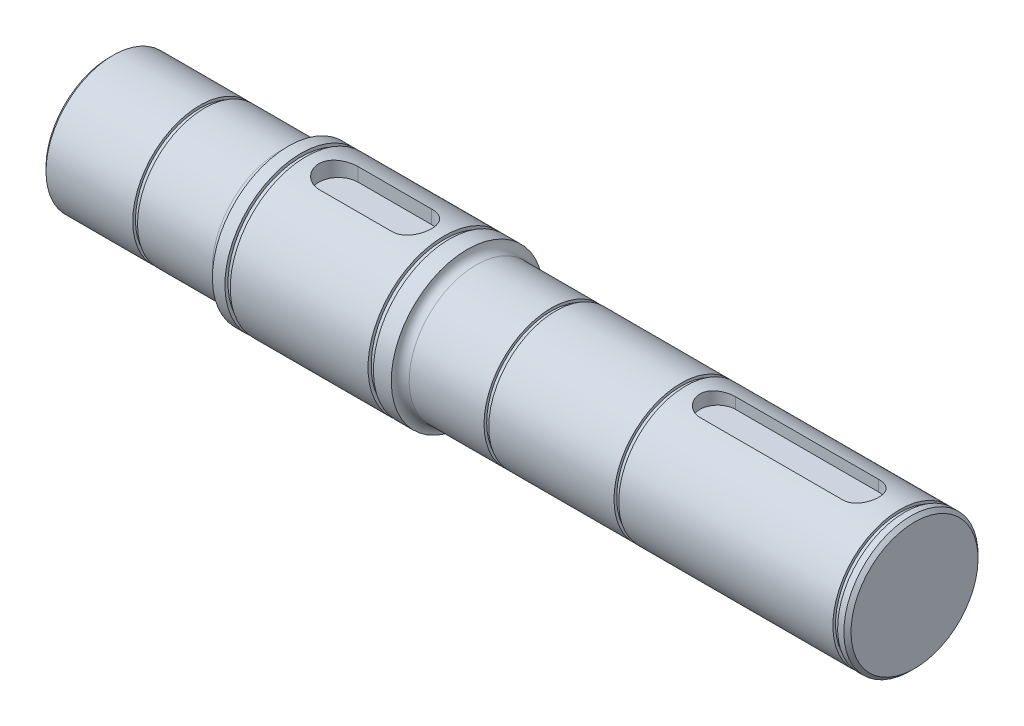
SolidWorks part; units mm, degrees
ref_plane "Front" through (0, 0, 0) normal (0, 0, 1) x (1, 0, 0)
ref_plane "Top" through (0, 0, 0) normal (0, 1, 0) x (1, 0, 0)
ref_plane "Right" through (0, 0, 0) normal (1, 0, 0) x (0, 0, -1)
sketch "Esquisse1" plane through (0, 0, 0) normal (0, 0, 1) x (1, 0, 0)
  line L0 (0, 0) -> (0, 37.5)
  line L1 (0, 37.5) -> (95, 37.5)
  line L3 (100, 42.5) -> (200, 42.5)
  line L5 (205, 37.5) -> (450, 37.5)
  line L6 (450, 37.5) -> (450, 0)
  line L7 (450, 0) -> (0, 0)
  arc A0 (100, 42.5) -> (95, 37.5) centre (95, 42.5) cw
  arc A1 (200, 42.5) -> (205, 37.5) centre (205, 42.5) ccw
  dimension "D4" = 5
  dimension "D6" = 5
  dimension "D1" = 37.5
  dimension "D2" = 100
  dimension "D3" = 450
  dimension "D5" = 42.5
  dimension "D7" = 100
revolve "Révolution1" add sketch "Esquisse1" angle 360 about L7
ref_plane "Plan1" through (110, 0, 0) normal (1, 0, 0) x (0, 0, -1)
ref_plane "Plan2" through (190, 0, 0) normal (1, 0, 0) x (0, 0, -1)
sketch "Esquisse2" plane through (110, 0, 0) normal (1, 0, 0) x (0, 0, -1)
  circle A0 centre (0, 0) radius 42.5 construction
  circle A2 centre (0, 0) radius 42.5
  circle A3 centre (0, 0) radius 40.75
  dimension "D1" = 1.75
extrude "Enlèv. mat.-Extru.1" cut sketch "Esquisse2" against normal blind 3
sketch "Esquisse3" plane through (190, 0, 0) normal (1, 0, 0) x (0, 0, -1)
  circle A0 centre (0, 0) radius 42.5 construction
  circle A1 centre (0, 0) radius 42.5
  circle A2 centre (0, 0) radius 40.75
  dimension "D1" = 1.75
extrude "Enlèv. mat.-Extru.2" cut sketch "Esquisse3" against normal blind 3
ref_plane "Plan3" through (0, 42.5, 0) normal (0, 1, 0) x (1, 0, 0)
sketch "Esquisse4" plane through (0, 42.5, 0) normal (0, 1, 0) x (1, 0, 0)
  line L0 (148.5, 42.5) -> (148.5, 0) construction
  line L1 (187, 42.5) -> (110, 42.5) construction
  line L2 (128, 0) -> (169, 0) construction
  line L3 (128, 11) -> (169, 11)
  line L4 (128, -11) -> (169, -11)
  arc A0 (128, 11) -> (128, -11) centre (128, 0) ccw
  arc A1 (169, -11) -> (169, 11) centre (169, 0) ccw
  point P6 (148.5, 0)
  dimension "D2" = 11
  dimension "D1" = 41
extrude "Enlèv. mat.-Extru.3" cut sketch "Esquisse4" against normal blind 9
ref_plane "Plan4" through (0, 37.5, 0) normal (0, 1, 0) x (1, 0, 0)
sketch "Esquisse5" plane through (0, 37.5, 0) normal (0, 1, 0) x (1, 0, 0)
  line L0 (450, 0) -> (380, 0) construction
  line L1 (450, -37.5) -> (450, 37.5) construction
  line L2 (420, 0) -> (340, 0) construction
  line L3 (420, -10) -> (340, -10)
  line L4 (420, 10) -> (340, 10)
  arc A0 (420, -10) -> (420, 10) centre (420, 0) ccw
  arc A1 (340, 10) -> (340, -10) centre (340, 0) ccw
  point P7 (380, 0)
  dimension "D2" = 10
  dimension "D1" = 70
  dimension "D3" = 80
extrude "Enlèv. mat.-Extru.4" cut sketch "Esquisse5" against normal blind 7.5
chamfer "Chanfrein1" distance 2 angle 45 2 edges at (450, 37.5, 0) (0, 37.5, 0)
ref_plane "Plan5" through (444.5, 0, 0) normal (1, 0, 0) x (0, 0, -1)
sketch "Esquisse6" plane through (444.5, 0, 0) normal (1, 0, 0) x (0, 0, -1)
  circle A0 centre (0, 0) radius 37.5 construction
  circle A1 centre (0, 0) radius 37.5
  circle A2 centre (0, 0) radius 36
  dimension "D1" = 1.5
extrude "Enlèv. mat.-Extru.5" cut sketch "Esquisse6" against normal blind 2.65
ref_plane "Plan6" through (50.5, 0, 0) normal (-1, 0, 0) x (0, 0, 1)
sketch "Esquisse7" plane through (50.5, 0, 0) normal (-1, 0, 0) x (0, 0, 1)
  circle A0 centre (0, 0) radius 37.5 construction
  circle A1 centre (0, 0) radius 37.5
  circle A2 centre (0, 0) radius 36
  dimension "D1" = 1.5
extrude "Enlèv. mat.-Extru.6" cut sketch "Esquisse7" against normal blind 2.65
ref_plane "Plan8" through (249.5, 0, 0) normal (-1, 0, 0) x (0, 0, 1)
sketch "Esquisse8" plane through (249.5, 0, 0) normal (-1, 0, 0) x (0, 0, 1)
  circle A0 centre (0, 0) radius 37.5 construction
  circle A1 centre (0, 0) radius 37.5
  circle A2 centre (0, 0) radius 36
  dimension "D1" = 1.5
extrude "Enlèv. mat.-Extru.7" cut sketch "Esquisse8" along normal blind 2.65
ref_plane "Plan9" through (319.5, 0, 0) normal (1, 0, 0) x (0, 0, -1)
sketch "Esquisse10" plane through (319.5, 0, 0) normal (1, 0, 0) x (0, 0, -1)
  circle A0 centre (0, 0) radius 37.5 construction
  circle A1 centre (0, 0) radius 37.5
  circle A2 centre (0, 0) radius 36
  dimension "D1" = 1.5
extrude "Enlèv. mat.-Extru.11" cut sketch "Esquisse10" along normal blind 2.65
